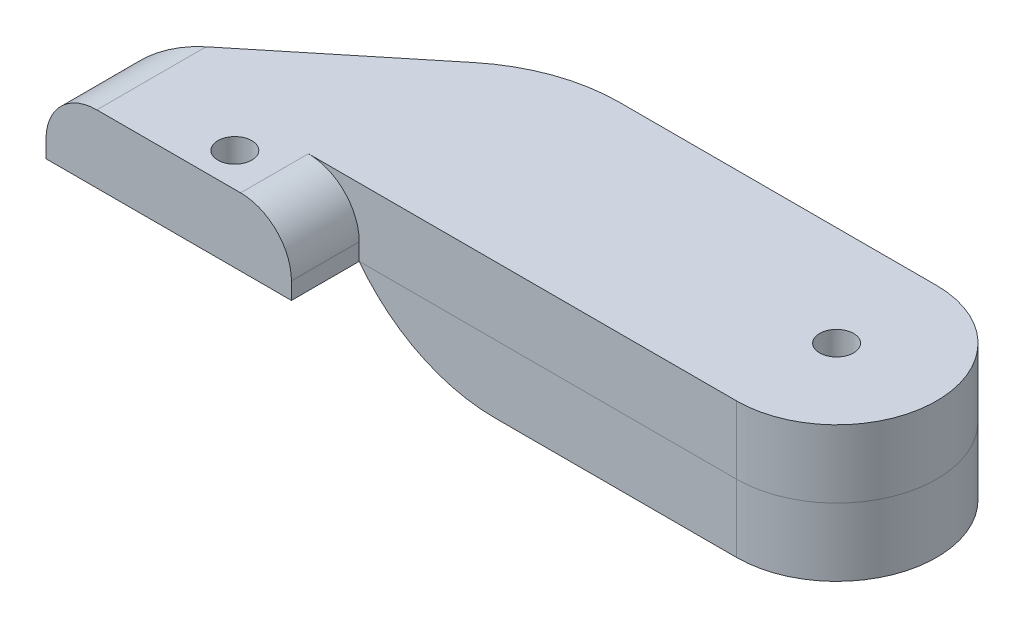
SolidWorks part; units mm, degrees
ref_plane "Front Plane" through (0, 0, 0) normal (0, 0, 1) x (1, 0, 0)
ref_plane "Top Plane" through (0, 0, 0) normal (0, 1, 0) x (1, 0, 0)
ref_plane "Right Plane" through (0, 0, 0) normal (1, 0, 0) x (0, 0, -1)
sketch "Sketch1" plane through (0, 0, 0) normal (0, 1, 0) x (1, 0, 0)
  line L0 (5.3578, 1.9995) -> (19.8378, 13.8)
  line L1 (5.3578, -1.9995) -> (19.8378, -1.9995)
  line L2 (5.3578, -1.9995) -> (5.3578, 1.9995)
  line L3 (5.3578, 1.9995) -> (19.8378, 1.9995) construction
  line L4 (19.8378, -1.9995) -> (19.8378, 1.9995)
  line L5 (5.3578, -1.9995) -> (19.8378, 1.9995) construction
  line L6 (5.3578, 1.9995) -> (19.8378, -1.9995) construction
  line L7 (19.8378, 13.8) -> (19.8378, 1.9995) construction
  line L8 (19.8378, 7.8997) -> (48.0003, 7.8997) construction
  line L11 (19.8378, 13.8) -> (42.1, 13.8)
  line L12 (42.1, 13.8) -> (42.1, 1.9995) construction
  line L13 (19.8378, 1.9995) -> (42.1, 1.9995)
  arc A2 (42.1, 13.8) -> (42.1, 1.9995) centre (42.1, 7.8997) cw
  point P0 (0, 0)
extrude "Boss-Extrude2" add sketch "Sketch1" along normal blind 4
ref_plane "Plane1" through (0, -4, 0) normal (0, -1, 0) x (-1, 0, 0)
sketch "Sketch2" plane through (0, 0, 0) normal (0, 1, 0) x (1, 0, 0)
  line L0 (42.1, 13.8) -> (42.1, 2) construction
  line L5 (26.1498, 7.9) -> (45.7842, 7.9) construction
  line L6 (42.1, 18.1892) -> (42.1, -2.3892) construction
  line L7 (27.9848, 9.8932) -> (39.8678, 10.8763) construction
  line L8 (27.9848, 5.9068) -> (39.8683, 4.9233) construction
  circle A9 centre (42.1, 7.9) radius 3.6842 construction
  arc A16 (27.9848, 9.8932) -> (27.9848, 5.9068) centre (28.1497, 7.9) ccw construction
  arc A17 (39.8678, 10.8763) -> (39.8683, 4.9233) centre (42.1, 7.9) ccw construction
  point P0 (53.3853, 10.5001)
  point P3 (46.1609, 22.3448)
  point P5 (49.6378, 19.3514)
  point P29 (51.9992, 11.3401)
  point P37 (42.1, 7.9)
ref_plane "Plane2" through (0, 0, 0) normal (0, -1, 0) x (-1, 0, 0)
sketch "Sketch4" plane through (0, 0, 0) normal (0, -1, 0) x (-1, 0, 0)
  line L1 (-19.8378, 2) -> (-42.1, 2)
  line L2 (-19.8378, 2) -> (-19.8378, 13.8)
  line L3 (-19.8378, 13.8) -> (-42.1, 13.8)
  line L4 (-42.1, 2) -> (-42.1, 13.8) construction
  arc A0 (-42.1, 2) -> (-42.1, 13.8) centre (-42.1, 7.9) cw
extrude "Boss-Extrude3" add sketch "Sketch4" along normal blind 4
ref_plane "Plane3" through (0, -4, 0) normal (0, -1, 0) x (-1, 0, 0)
sketch "Sketch6" plane through (0, -4, 0) normal (0, -1, 0) x (1, 0, 0)
  line L0 (39.8683, -4.9233) -> (27.9848, -5.9068)
  line L1 (27.9848, -5.9068) -> (39.8683, -4.9233) construction
  line L2 (27.9848, -9.8932) -> (39.8678, -10.8763)
  line L4 (42.1, -7.9) -> (26.1498, -7.9) construction
  line L5 (27.9848, -9.8932) -> (27.9848, -5.9068) construction
  circle A0 centre (42.1, -7.9) radius 3.6842 construction
  arc A1 (27.9848, -5.9068) -> (27.9848, -9.8932) centre (27.9848, -7.9) ccw
  arc A2 (27.9848, -5.9068) -> (27.9848, -9.8932) centre (28.1497, -7.9) ccw construction
  arc A3 (39.8683, -4.9233) -> (39.8678, -10.8763) centre (42.1, -7.9) cw
extrude "Cut-Extrude1" cut sketch "Sketch6" against normal blind 4
sketch "Sketch7" plane through (0, 0, 0) normal (0, -1, 0) x (1, 0, 0)
  circle A0 centre (42.1, -7.9) radius 1
extrude "Cut-Extrude2" cut sketch "Sketch7" against normal through all
sketch "Sketch9" plane through (0, 4, 0) normal (0, 1, 0) x (1, 0, 0)
  line L2 (19.8378, 0) -> (14.5, 0) construction
  line L3 (19.8378, -1.9995) -> (19.8378, 1.9995) construction
  circle A1 centre (14.5, 0) radius 1
extrude "Cut-Extrude8" cut sketch "Sketch9" against normal through all
fillet "Fillet1" radius 10 1 edges at (19.8378, -4, -7.9)
fillet "Fillet2" radius 10 1 edges at (19.8378, 2, -13.8)
fillet "Fillet3" radius 3 2 edges at (5.3578, 4, 0) (19.8378, 4, 0)
